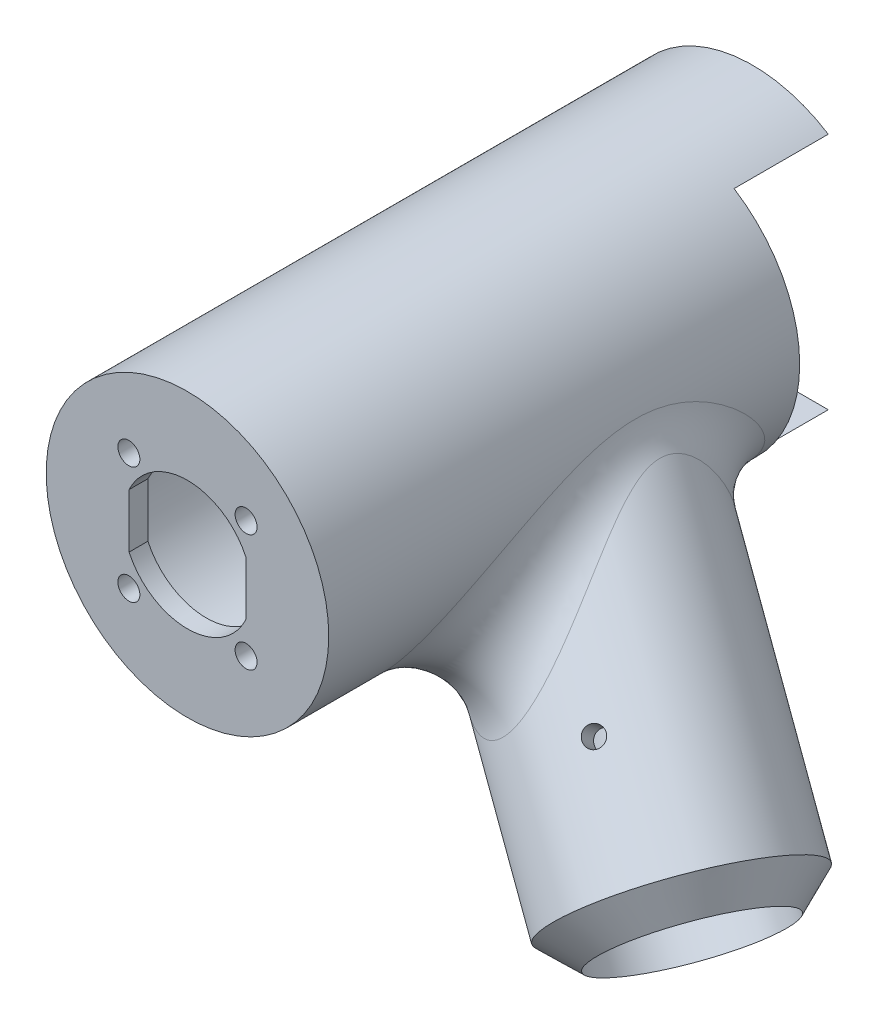
SolidWorks part; units mm, degrees
material "ABS"
ref_plane "Front Plane" through (0, 0, 0) normal (0, 0, 1) x (1, 0, 0)
ref_plane "Top Plane" through (0, 0, 0) normal (0, 1, 0) x (1, 0, 0)
ref_plane "Right Plane" through (0, 0, 0) normal (1, 0, 0) x (0, 0, -1)
sketch "Sketch1" plane through (0, 0, 0) normal (0, 0, 1) x (1, 0, 0)
  circle A0 centre (0, 0) radius 22.5
  dimension "D1" = 45
extrude "Boss-Extrude1" add sketch "Sketch1" along normal blind 90
sketch "Sketch2" plane through (0, 0, 0) normal (0, 0, -1) x (-1, 0, 0)
  circle A0 centre (0, 0) radius 16
  circle A1 centre (0, 0) radius 22.5 construction
  dimension "D1" = 6.5
extrude "Cut-Extrude1" cut sketch "Sketch2" against normal offset from surface (87 mm away) 3 up to face at (22.5, 0, 90)
sketch "Sketch3" plane through (0, 0, 0) normal (1, 0, 0) x (0, 0, -1)
  line L1 (15, -19) -> (-15, -19)
  line L2 (15, -19) -> (15, 19)
  line L3 (15, 19) -> (-15, 19)
  line L4 (-15, -19) -> (-15, 19)
  line L5 (15, -19) -> (-15, 19) construction
  line L6 (15, 19) -> (-15, -19) construction
  point P0 (0, 0)
  dimension "D1" = 15
  dimension "D2" = 38
extrude "Cut-Extrude2" cut sketch "Sketch3" along normal blind 33
sketch "Sketch4" plane through (0, 0, 0) normal (1, 0, 0) x (0, 0, -1)
  line L0 (0, 0) -> (-40, 0) construction
  line L1 (0, -22.5) -> (0, 22.5) construction
  line L2 (-10, 15) -> (-60, 15)
  line L3 (-10, 15) -> (-10, -15)
  line L4 (-10, -15) -> (-60, -15)
  line L5 (-60, 15) -> (-60, -15)
  line L6 (-10, 15) -> (-60, -15) construction
  line L7 (-10, -15) -> (-60, 15) construction
  point P2 (-35, 0)
  dimension "D1" = 50
  dimension "D2" = 10
  dimension "D3" = 30
ref_plane "Plane2" through (0, 0, 35) normal (0, 0, -1) x (-1, 0, 0)
sketch3d "3DSketch1"
  line L0 (0, 0, 35) -> (120, -120, 90)
sketch "Sketch5" plane through (0, 0, 35) normal (0, 0, -1) x (-1, 0, 0)
  line L0 (0, 0) -> (-54.3806, -54.3806)
  line L1 (0, 15) -> (0, -15) construction
  dimension "D1" = 45
ref_plane "Plane3" through (0, 0, 35) normal (0.6727, -0.6727, 0.3083) x (0.218, -0.218, -0.9513)
sketch "Sketch6" plane through (0, 0, 35) normal (0.6727, -0.6727, 0.3083) x (0.218, -0.218, -0.9513)
  circle A0 centre (0, 0) radius 17.5
  dimension "D1" = 35
extrude "Boss-Extrude2" add sketch "Sketch6" along normal blind 70
sketch "Sketch7" plane through (54.3448, -54.3448, 24.908) normal (0.6727, -0.6727, 0.3083) x (0.218, -0.218, -0.9513)
  circle A0 centre (-33.2951, 0) radius 12.9
  dimension "D1" = 25.8
extrude "Cut-Extrude3" cut sketch "Sketch7" against normal blind 50
sketch "Sketch8" plane through (0, 0, 0) normal (0, 0, -1) x (-1, 0, 0)
  circle A0 centre (0, 0) radius 19.5
extrude "Cut-Extrude4" cut sketch "Sketch8" against normal blind 61
fillet "Fillet1" radius 10 1 edges at (22.3843, 2.2789, 41.1361)
chamfer "Chamfer1" distance 5 angle 45 1 edges at (59.4607, -34.712, 56.5812)
ref_plane "Plane4" through (12.052, -19, 15) normal (0.7354, 0.6538, -0.178) x (-0.459, 0.2874, -0.8407)
sketch "Sketch9" plane through (12.052, -19, 15) normal (0.7354, 0.6538, -0.178) x (-0.459, 0.2874, -0.8407)
  line L0 (-55.3018, -12.6166) -> (-46.2319, -4.8898) construction
  line L1 (-43.9531, -25.9379) -> (-66.6504, 0.7047) construction
  line L2 (-5.8225, 29.5355) -> (-141.6207, -86.1531) construction
  circle A0 centre (-41.5998, -0.9437) radius 1.5
  dimension "D1" = 3
  dimension "D2" = 18
extrude "Cut-Extrude5" cut sketch "Sketch9" against normal blind 63
sketch "Sketch10" plane through (0, 0, 61) normal (0, 0, -1) x (-1, 0, 0)
  circle A0 centre (0, 0) radius 16 construction
  circle A1 centre (0, 0) radius 19.5
  circle A2 centre (0, 0) radius 19.5
  circle A3 centre (0, 0) radius 16
  dimension "D1" = 0
extrude "Boss-Extrude4" add sketch "Sketch10" along direction (0, 0, 1) on the side of the normal offset from surface (36 mm away) 25 up to face at (-6.3901, 0, 0)
sketch "Sketch11" plane through (0, 0, 87) normal (0, 0, -1) x (-1, 0, 0)
  line L0 (-9.3, -4.3096) -> (-9.3, 4.3096)
  line L1 (0, -10.25) -> (0, 13.1651) construction
  line L2 (9.3, -4.3096) -> (9.3, 4.3096)
  arc A0 (-9.3, -4.3096) -> (9.3, -4.3096) centre (0, 0) ccw
  arc A1 (9.3, 4.3096) -> (-9.3, 4.3096) centre (0, 0) ccw
  circle A2 centre (0, 13.2) radius 1.75
  circle A3 centre (9.3338, 9.3338) radius 1.75
  circle A4 centre (13.2, 0) radius 1.75
  circle A5 centre (9.3338, -9.3338) radius 1.75
  circle A6 centre (0, -13.2) radius 1.75
  circle A7 centre (-9.3338, -9.3338) radius 1.75
  circle A8 centre (-13.2, 0) radius 1.75
  circle A9 centre (-9.3338, 9.3338) radius 1.75
  dimension "D1" = 20.5
  dimension "D3" = 3.5
  dimension "D2" = 9.3
  dimension "D4" = 13.2
  dimension "D5" = 8
extrude "Cut-Extrude6" cut sketch "Sketch11" against normal blind 20.5 contours A7 | L0 A1 L2 A0 | A5 | A3 | A9 region at (9.3338, -9.3338, 87)
pattern_circular "CirPattern1" count 3 over 360 about axis through (13.4532, -13.4532, 41.1661) along (0.6727, -0.6727, 0.3083) of "Cut-Extrude5" reverse direction yes
